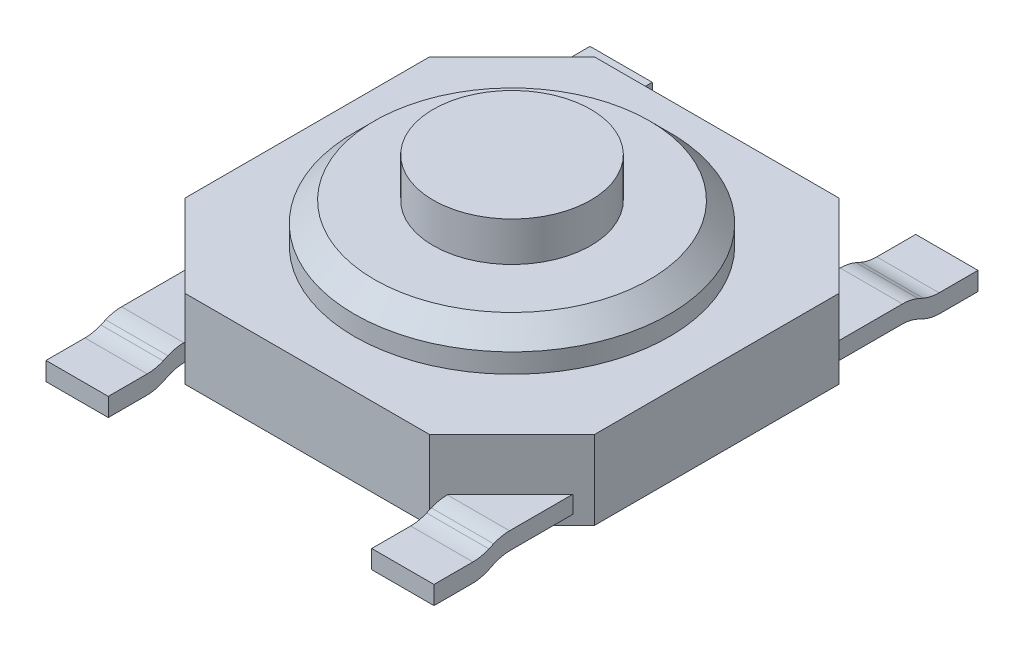
SolidWorks part; units mm, degrees
ref_plane "Front Plane" through (0, 0, 0) normal (0, 0, 1) x (1, 0, 0)
ref_plane "Top Plane" through (0, 0, 0) normal (0, 1, 0) x (1, 0, 0)
ref_plane "Right Plane" through (0, 0, 0) normal (1, 0, 0) x (0, 0, -1)
sketch "Sketch1" plane through (0, 0, 0) normal (0, 1, 0) x (1, 0, 0)
  line L0 (-3.1152, 1.9722) -> (-2.07, 3.0174)
  line L1 (-2.07, 3.0174) -> (1.0396, 3.0174)
  line L2 (1.0396, 3.0174) -> (2.0848, 1.9722)
  line L3 (2.0848, 1.9722) -> (2.0848, -1.1374)
  line L4 (2.0848, -1.1374) -> (1.0396, -2.1826)
  line L5 (1.0396, -2.1826) -> (-2.07, -2.1826)
  line L6 (-2.07, -2.1826) -> (-3.1152, -1.1374)
  line L7 (-3.1152, -1.1374) -> (-3.1152, 1.9722)
  line L8 (-3.1152, 1.9722) -> (2.0848, 1.9722) construction
  line L9 (-3.1152, -1.1374) -> (2.0848, -1.1374) construction
  line L10 (-2.07, 3.0174) -> (-2.07, -2.1826) construction
  line L11 (1.0396, -2.1826) -> (1.0396, 3.0174) construction
  point P5 (-3.1152, 0.4174)
  dimension "D1" = 5.2
  dimension "D2" = 5.2
extrude "Boss-Extrude1" add sketch "Sketch1" along normal blind 1
sketch "Sketch4" plane through (0, 1, 0) normal (0, 1, 0) x (1, 0, 0)
  line L0 (-0.5152, 3.0174) -> (-0.5152, -2.1826) construction
  line L1 (1.0396, 3.0174) -> (-2.07, 3.0174) construction
  line L2 (-2.07, -2.1826) -> (1.0396, -2.1826) construction
  line L3 (-3.1152, 0.4174) -> (2.0848, 0.4174) construction
  line L4 (-3.1152, 1.9722) -> (-3.1152, -1.1374) construction
  line L5 (2.0848, -1.1374) -> (2.0848, 1.9722) construction
  circle A1 centre (-0.5152, 0.4174) radius 2
  point P14 (0, 0)
  dimension "D1" = 4
extrude "Boss-Extrude3" add sketch "Sketch4" along normal blind 0.5
sketch "Sketch2" plane through (0, 1.5, 0) normal (0, 1, 0) x (1, 0, 0)
  line L0 (-0.5152, 3.0174) -> (-0.5152, -2.1826) construction
  line L1 (1.0396, 3.0174) -> (-2.07, 3.0174) construction
  line L2 (-2.07, -2.1826) -> (1.0396, -2.1826) construction
  line L3 (-3.1152, 0.4174) -> (2.0848, 0.4174) construction
  line L4 (-3.1152, 1.9722) -> (-3.1152, -1.1374) construction
  line L5 (2.0848, -1.1374) -> (2.0848, 1.9722) construction
  circle A0 centre (-0.5152, 0.4174) radius 1
  point P14 (-0.72, -0.2584)
  dimension "D1" = 2
extrude "Boss-Extrude2" add sketch "Sketch2" along normal blind 0.5
chamfer "Chamfer1" distance 0.254 1 edges at (-0.5152, 1.5, 1.5826)
sketch "Sketch5" plane through (0, 0, 2.1826) normal (0, 0, 1) x (1, 0, 0)
  line L0 (-0.5152, 1) -> (-0.5152, 0) construction
  line L1 (-2.9786, 0.3438) -> (-2.1879, 0.3438)
  line L2 (-2.9786, 0.3438) -> (-2.9786, 0.1233)
  line L3 (-2.9786, 0.1233) -> (-2.1879, 0.1233)
  line L4 (-2.1879, 0.3438) -> (-2.1879, 0.1233)
  line L5 (-2.07, 1) -> (1.0396, 1) construction
  line L6 (-2.07, 0) -> (1.0396, 0) construction
  line L7 (1.1575, 0.3438) -> (1.1575, 0.1233)
  line L8 (1.9481, 0.1233) -> (1.1575, 0.1233)
  line L9 (1.9481, 0.3438) -> (1.9481, 0.1233)
  line L10 (1.9481, 0.3438) -> (1.1575, 0.3438)
extrude "Boss-Extrude4" add sketch "Sketch5" against normal blind 1.644 separate body
ref_plane "Plane3" through (0, 0, 2.4366) normal (0, 0, 1) x (1, 0, 0)
sketch "Sketch7" plane through (0, 0, 2.4366) normal (0, 0, 1) x (1, 0, 0)
  line L0 (-3.1152, 0) -> (-2.07, 0) construction
  line L1 (-2.9786, 0) -> (-2.1879, 0)
  line L2 (-2.9786, 0) -> (-2.9786, 0.2336)
  line L3 (-2.9786, 0.2336) -> (-2.1879, 0.2336)
  line L4 (-2.1879, 0) -> (-2.1879, 0.2336)
  line L5 (-2.1879, 0.1233) -> (-2.1879, 0.3438) construction
  line L6 (-2.9786, 0.3438) -> (-2.9786, 0.1233) construction
  line L7 (-0.5152, 1) -> (-0.5152, 0) construction
  line L8 (-2.07, 1) -> (1.0396, 1) construction
  line L9 (-2.07, 0) -> (1.0396, 0) construction
  line L10 (1.1575, 0) -> (1.1575, 0.2336)
  line L11 (1.9481, 0.2336) -> (1.1575, 0.2336)
  line L12 (1.9481, 0) -> (1.9481, 0.2336)
  line L13 (1.9481, 0) -> (1.1575, 0)
extrude "Boss-Extrude5" add sketch "Sketch7" along normal blind 0.6 separate body
loft "Loft1" add section face at (1.5528, 0.1168, 2.4366) section face at (1.5528, 0.2336, 2.1826) connector at (1.9481, 0, 2.4366) connector at (1.9481, 0.1233, 2.1826)
loft "Loft2" add section face at (-2.5833, 0.1168, 2.4366) section face at (-2.5833, 0.2336, 2.1826) connector at (-2.1879, 0.2336, 2.4366) connector at (-2.1879, 0.3438, 2.1826)
fillet "Fillet1" radius 0.508 8 edges at (-2.5833, 0.3438, 2.1826) (-2.5833, 0.1233, 2.1826)
ref_axis "Axis1" through (2.0848, 0, -0.4174) along (-1, 0, 0)
ref_plane "Plane2" through (0, 0, -0.4174) normal (0, 0, 1) x (1, 0, 0)
mirror "Mirror1" about plane through (0, 0, -0.4174) normal (0, 0, 1) of "Boss-Extrude4", "Boss-Extrude5", "Loft1", "Loft2", "Fillet1"
